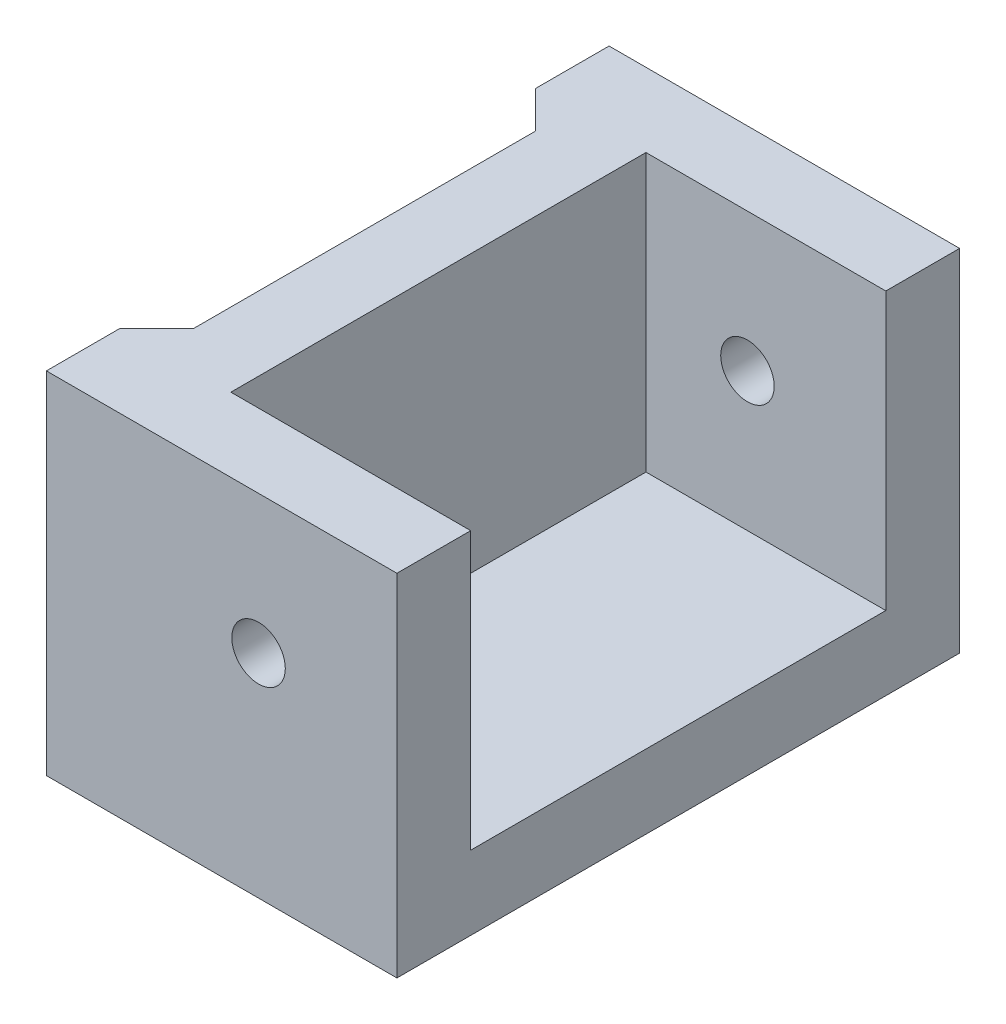
SolidWorks part; units mm, degrees
ref_plane "Front Plane" through (0, 0, 0) normal (0, 0, 1) x (1, 0, 0)
ref_plane "Top Plane" through (0, 0, 0) normal (0, 1, 0) x (1, 0, 0)
ref_plane "Right Plane" through (0, 0, 0) normal (1, 0, 0) x (0, 0, -1)
sketch "Sketch1" plane through (0, 0, 0) normal (0, 0, 1) x (1, 0, 0)
  line L1 (0, 0) -> (21.59, 0)
  line L2 (0, 0) -> (0, 5.08)
  line L3 (5.08, 5.08) -> (21.59, 5.08)
  line L4 (21.59, 0) -> (21.59, 5.08)
  line L6 (0, 5.08) -> (0, 21.59)
  line L7 (0, 21.59) -> (5.08, 21.59)
  line L8 (5.08, 5.08) -> (5.08, 21.59)
  dimension "D1" = 21.59
  dimension "D2" = 21.59
  dimension "D3" = 5.08
  dimension "D4" = 5.08
extrude "Boss-Extrude1" add sketch "Sketch1" along normal blind 38.735
sketch "Sketch2" plane through (0, 0, 38.735) normal (0, 0, 1) x (1, 0, 0)
  line L0 (0, 21.59) -> (0, 0) construction
  line L5 (0, 0) -> (21.59, 0) construction
  line L6 (5.08, 21.59) -> (0, 21.59) construction
  line L7 (-2.54, -2.54) -> (21.59, -2.54)
  line L8 (-2.54, -2.54) -> (-2.54, 21.59)
  line L9 (-2.54, 21.59) -> (21.59, 21.59)
  line L10 (21.59, -2.54) -> (21.59, 21.59)
  line L11 (21.59, 0) -> (21.59, 5.08) construction
  circle A0 centre (12.065, 12.065) radius 1.8415
  dimension "D1" = 12.065
  dimension "D2" = 12.065
  dimension "D3" = 3.683
  dimension "D4" = 2.54
  dimension "D5" = 2.54
extrude "Boss-Extrude2" add sketch "Sketch2" against normal blind 5.08
sketch "Sketch3" plane through (0, 0, 0) normal (0, 0, -1) x (-1, 0, 0)
  line L5 (2.54, -2.54) -> (-21.59, -2.54)
  line L6 (2.54, -2.54) -> (2.54, 21.59)
  line L7 (2.54, 21.59) -> (-21.59, 21.59)
  line L8 (-21.59, -2.54) -> (-21.59, 21.59)
  circle A0 centre (-12.065, 12.065) radius 1.8415
extrude "Boss-Extrude3" add sketch "Sketch3" against normal blind 5.08
sketch "Sketch4" plane through (21.59, 0, 0) normal (1, 0, 0) x (0, 0, -1)
  line L0 (0, -2.54) -> (0, 21.59) construction
  line L1 (-38.735, -2.54) -> (0, -2.54)
  line L2 (-38.735, -2.54) -> (-38.735, 3.3359)
  line L3 (-38.735, 3.3359) -> (0, 3.3359)
  line L4 (0, -2.54) -> (0, 3.3359)
extrude "Boss-Extrude5" add sketch "Sketch4" against normal up to surface (21.59 mm away) up to face at (0, 10.795, 19.3675)
sketch "Sketch5" plane through (21.59, 0, 0) normal (1, 0, 0) x (0, 0, -1)
  line L0 (-5.08, 21.59) -> (-5.08, 5.08) construction
  line L1 (-33.655, 5.08) -> (-5.08, 5.08)
  line L2 (-33.655, 5.08) -> (-33.655, 2.54)
  line L3 (-33.655, 2.54) -> (-5.08, 2.54)
  line L4 (-5.08, 5.08) -> (-5.08, 2.54)
  dimension "D1" = 2.54
extrude "Cut-Extrude1" cut sketch "Sketch5" against normal up to surface (16.51 mm away) up to face at (5.08, 13.335, 19.3675)
chamfer "Chamfer2" distance 2.54 angle 45 2 edges at (0, 9.525, 33.655) (0, 9.525, 5.08)
